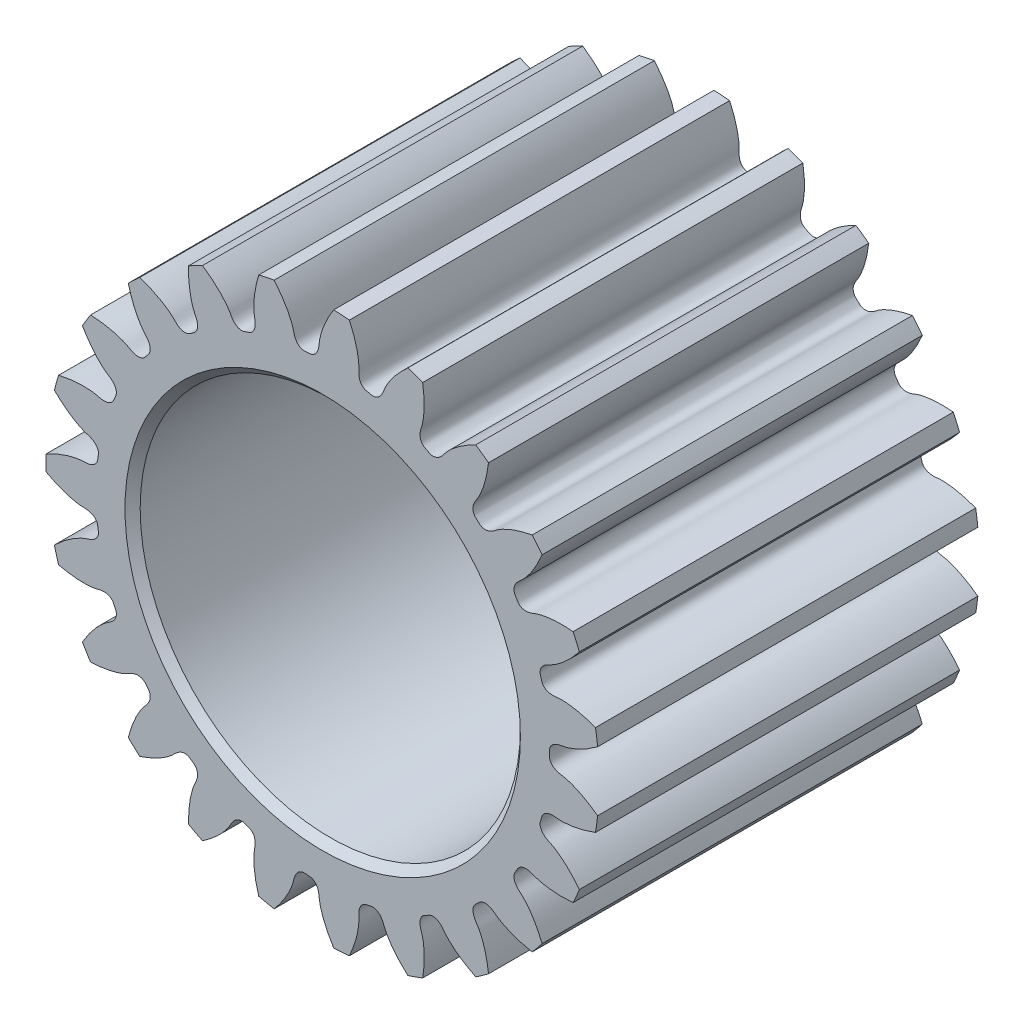
SolidWorks part; units mm, degrees
ref_plane "Front Plane" through (0, 0, 0) normal (0, 0, 1) x (1, 0, 0)
ref_plane "Top Plane" through (0, 0, 0) normal (0, 1, 0) x (1, 0, 0)
ref_plane "Right Plane" through (0, 0, 0) normal (1, 0, 0) x (0, 0, -1)
ref_axis "Axis1" through (0, 0, 55) along (0, 0, -1)
sketch "SketchRevolvePlanet_Revolving_Follower02" plane through (0, 0, 0) normal (1, 0, 0) x (0, 0, -1)
  line L0 (0, 0) -> (25.4, 0) construction
  line L1 (-6.35, 0) -> (-6.35, 9.2371)
  line L2 (-6.35, 9.2371) -> (6.35, 9.2371)
  line L3 (6.35, 9.2371) -> (6.35, 0)
  line L4 (6.35, 0) -> (-6.35, 0)
  dimension "Side1" = 6.35
  dimension "OutsideRadius" = 9.2371
  dimension "Side2" = 6.35
revolve "Planet_Revolving_Follower02" add sketch "SketchRevolvePlanet_Revolving_Follower02" angle 360 about L0
sketch "SketchToothPlanet_Revolving_Follower02" plane through (0, 0, 0) normal (0, 0, 1) x (1, 0, 0)
  arc A0 (9.2175, 1.0226) -> (9.2175, -1.0226) centre (0, 0) cw
  spline S0 degree 3 poles (9.2175, -1.0226) (9.1145, -0.9453) (8.9768, -0.8504) (8.8027, -0.7458) (8.7086, -0.693) (8.6192, -0.6462) (8.5346, -0.6051) (8.4553, -0.5694) (8.3813, -0.5387) (8.313, -0.5126) (8.2505, -0.4909) (8.1941, -0.4731) (8.1439, -0.4589) (8.1, -0.4479) (8.0328, -0.4328) (7.9723, -0.426) (7.9186, -0.4147) (7.8984, -0.41) (7.8787, -0.4048) (7.8594, -0.3992) (7.8405, -0.3931) (7.822, -0.3865) (7.8038, -0.3793) (7.7858, -0.3715) (7.7682, -0.3631) (7.7508, -0.354) (7.7337, -0.344) (7.7167, -0.333) (7.7, -0.321) (7.6835, -0.3077) (7.6672, -0.293) (7.6513, -0.2767) (7.636, -0.2585) (7.6214, -0.2382) (7.6079, -0.2157) (7.596, -0.1908) (7.5861, -0.1638) (7.5788, -0.1348) (7.5749, -0.1063) (7.5732, -0.0613) (7.5754, 0) (7.5732, 0.0613) (7.5749, 0.1063) (7.5788, 0.1348) (7.5861, 0.1638) (7.596, 0.1908) (7.6079, 0.2157) (7.6214, 0.2382) (7.636, 0.2585) (7.6513, 0.2767) (7.6672, 0.293) (7.6835, 0.3077) (7.7, 0.321) (7.7167, 0.333) (7.7337, 0.344) (7.7508, 0.354) (7.7682, 0.3631) (7.7858, 0.3715) (7.8038, 0.3793) (7.822, 0.3865) (7.8405, 0.3931) (7.8594, 0.3992) (7.8787, 0.4048) (7.8984, 0.41) (7.9186, 0.4147) (7.9723, 0.426) (8.0328, 0.4328) (8.1, 0.4479) (8.1439, 0.4589) (8.1941, 0.4731) (8.2505, 0.4909) (8.313, 0.5126) (8.3813, 0.5387) (8.4553, 0.5694) (8.5346, 0.6051) (8.6192, 0.6462) (8.7086, 0.693) (8.8027, 0.7458) (8.9768, 0.8504) (9.1145, 0.9453) (9.2175, 1.0226) knots 0 0 0 0 0.094202 0.12221 0.14852 0.173134 0.196049 0.217267 0.236788 0.254611 0.270737 0.285166 0.297897 0.30893 0.318266 0.34824 0.353361 0.358399 0.363362 0.368259 0.373101 0.377898 0.382666 0.387419 0.392177 0.396959 0.40179 0.406696 0.411707 0.416858 0.422185 0.427725 0.433517 0.439594 0.445983 0.452694 0.459717 0.467016 0.474526 0.480668 0.5 0.519332 0.525474 0.532984 0.540283 0.547306 0.554017 0.560406 0.566483 0.572275 0.577815 0.583142 0.588293 0.593304 0.59821 0.603041 0.607823 0.612581 0.617334 0.622102 0.626899 0.631741 0.636638 0.641601 0.646639 0.65176 0.681734 0.69107 0.702103 0.714834 0.729263 0.745389 0.763212 0.782733 0.803951 0.826866 0.85148 0.87779 0.905798 1 1 1 1
extrude "ToothExtrudeCutPlanet_Revolving_Follower02" cut sketch "SketchToothPlanet_Revolving_Follower02" against normal blind 6.35 and the other way blind 6.35
ref_axis "Axis2" through (10.1997, 0, 0) along (-1, 0, 0)
ref_plane "Plane1" through (0, 0, 0) normal (0, 0, -1) x (1, 0, 0)
pattern_circular "PatternPlanet_Revolving_Follower02" count 23 every 15.652 about axis through (0, 0, 55) along (0, 0, -1) of "ToothExtrudeCutPlanet_Revolving_Follower02"
sketch "BoreRevolveSketch" plane through (0, 0, 0) normal (1, 0, 0) x (0, 0, -1)
  line L0 (0, 0) -> (25.4, 0) construction
  line L1 (-6.35, 0) -> (6.35, 0)
  line L2 (6.35, 0) -> (6.35, 6.604)
  line L3 (6.35, 6.604) -> (6.096, 6.35)
  line L4 (6.096, 6.35) -> (-6.096, 6.35)
  line L5 (-6.096, 6.35) -> (-6.35, 6.604)
  line L6 (-6.35, 6.604) -> (-6.35, 0)
  dimension "BoreSide1" = 6.35
  dimension "TaperSide1" = 6.604
  dimension "Chamfer1X" = 0.254
  dimension "Chamfer1Y" = 0.254
  dimension "BoreSide2" = 6.35
  dimension "TaperSide2" = 6.604
revolve "BoreRevolveCut" cut sketch "BoreRevolveSketch" angle 360 about L0
sketch "AuxiliarySketchPlanet_Revolving_Follower02" plane through (0, 0, 0) normal (0, 0, 1) x (1, 0, 0)
  circle A0 centre (0, 0) radius 8.4982 construction
  circle A1 centre (0, 0) radius 7.9857 construction
  circle A2 centre (0, 0) radius 8.0107 construction
  circle A3 centre (0, 0) radius 9.2371 construction
  circle A4 centre (0, 0) radius 7.5745 construction
  dimension "PitchDiameter" = 16.9963
  dimension "BaseDiameter" = 15.9713
  dimension "FormDiameter" = 16.0213
  dimension "MajorDiameter" = 18.4743
  dimension "MinorDiameter" = 15.1489
